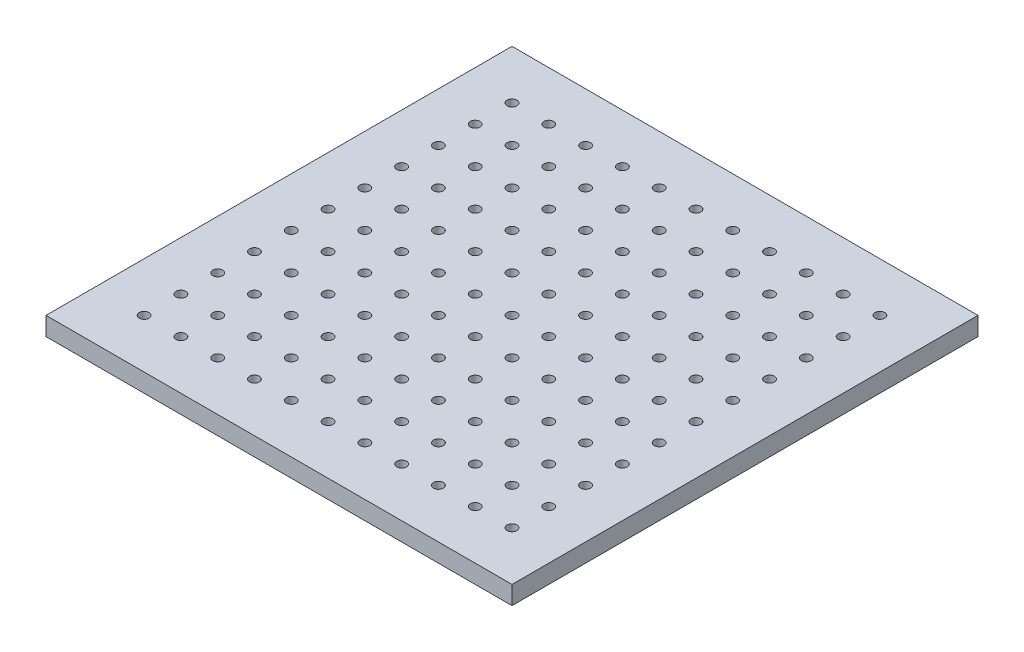
SolidWorks part; units mm, degrees
ref_plane "Plano frontal" through (0, 0, 0) normal (0, 0, 1) x (1, 0, 0)
ref_plane "Plano superior" through (0, 0, 0) normal (0, 1, 0) x (1, 0, 0)
ref_plane "Plano direito" through (0, 0, 0) normal (1, 0, 0) x (0, 0, -1)
sketch "Esboço1" plane through (0, 0, 0) normal (0, 1, 0) x (1, 0, 0)
  line L1 (-190, -190) -> (190, -190)
  line L2 (-190, -190) -> (-190, 190)
  line L3 (-190, 190) -> (190, 190)
  line L4 (190, -190) -> (190, 190)
  line L5 (-190, -190) -> (190, 190) construction
  line L6 (-190, 190) -> (190, -190) construction
  point P0 (0, 0)
  dimension "D1" = 380
  dimension "D2" = 380
extrude "Ressalto-extrusão1" add sketch "Esboço1" along normal blind 15
sketch "Esboço2" plane through (0, 15, 0) normal (0, 1, 0) x (1, 0, 0)
  line L0 (-190, -190) -> (190, -190) construction
  line L1 (-190, 190) -> (-190, -190) construction
  circle A0 centre (-150, -150) radius 4
  dimension "D1" = 8
  dimension "D2" = 40
  dimension "D3" = 40
extrude "Corte-extrusão1" cut sketch "Esboço2" against normal through all
pattern_linear "Padrão linear1" count 11 spacing 30 along (1, 0, 0) count 11 spacing 30 along (0, 0, -1) of "Corte-extrusão1"
